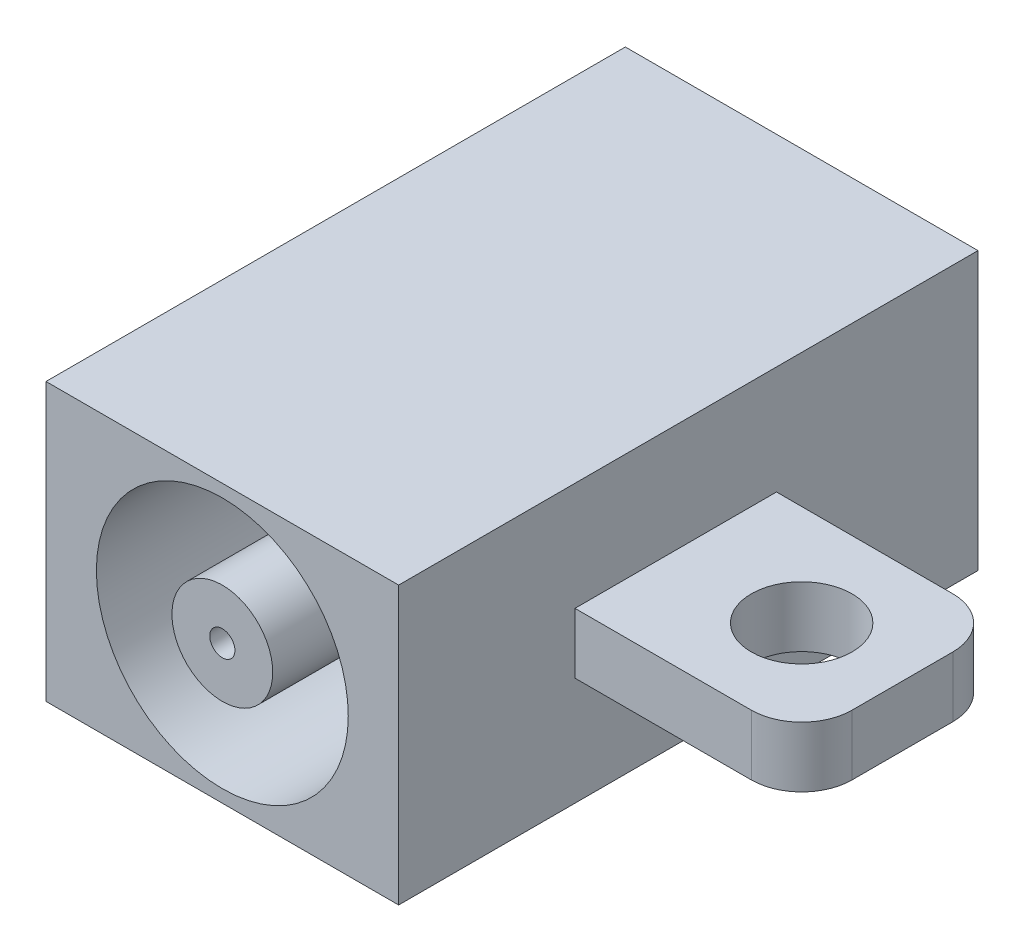
SolidWorks part; units mm, degrees
ref_plane "Front Plane" through (0, 0, 0) normal (0, 0, 1) x (1, 0, 0)
ref_plane "Top Plane" through (0, 0, 0) normal (0, 1, 0) x (1, 0, 0)
ref_plane "Right Plane" through (0, 0, 0) normal (1, 0, 0) x (0, 0, -1)
sketch "Sketch1" plane through (0, 0, 0) normal (0, 1, 0) x (1, 0, 0)
  line L1 (0, 0) -> (7, 0)
  line L2 (0, 0) -> (0, 11.5)
  line L3 (0, 11.5) -> (7, 11.5)
  line L4 (7, 0) -> (7, 11.5)
  dimension "D1" = 11.5
  dimension "D2" = 7
extrude "Boss-Extrude1" add sketch "Sketch1" along normal blind 5.5
sketch "Sketch2" plane through (0, 0, 0) normal (0, 0, 1) x (1, 0, 0)
  line L1 (0, 0) -> (7, 0) construction
  line L2 (7, 5.5) -> (7, 0) construction
  circle A0 centre (3.5, 2.75) radius 2.5
  dimension "D1" = 5
  dimension "D2" = 2.75
  dimension "D3" = 3.5
extrude "Cut-Extrude1" cut sketch "Sketch2" against normal blind 5.5
sketch "Sketch3" plane through (0, 0, 0) normal (0, 0, 1) x (1, 0, 0)
  circle A0 centre (3.5, 2.75) radius 1
  dimension "D1" = 2
extrude "Boss-Extrude2" add sketch "Sketch3" against normal blind 5.5
sketch "Sketch4" plane through (0, 0, 0) normal (0, 0, 1) x (1, 0, 0)
  circle A0 centre (3.5, 2.75) radius 0.25
  dimension "D1" = 0.5
extrude "Cut-Extrude2" cut sketch "Sketch4" against normal blind 5.5
sketch "Sketch5" plane through (7, 0, 0) normal (1, 0, 0) x (0, 0, -1)
  line L0 (0, 5.5) -> (0, 0) construction
  line L1 (3.5, 3.35) -> (7.5, 3.35)
  line L2 (3.5, 3.35) -> (3.5, 2.15)
  line L3 (3.5, 2.15) -> (7.5, 2.15)
  line L4 (7.5, 3.35) -> (7.5, 2.15)
  line L6 (0, 0) -> (11.5, 0) construction
  dimension "D1" = 3.5
  dimension "D2" = 1.2
  dimension "D3" = 4
  dimension "D4" = 2.15
extrude "Boss-Extrude3" add sketch "Sketch5" along normal blind 4.5
fillet "Fillet1" radius 1 2 edges at (11.5, 2.75, -7.5) (11.5, 2.75, -3.5)
sketch "Sketch6" plane through (0, 3.35, 0) normal (0, 1, 0) x (1, 0, 0)
  line L1 (10.5, 3.5) -> (7, 3.5) construction
  line L2 (11.5, 6.5) -> (11.5, 4.5) construction
  circle A0 centre (9.5, 5.5) radius 1
  dimension "D1" = 2
  dimension "D2" = 2
  dimension "D3" = 2
extrude "Cut-Extrude3" cut sketch "Sketch6" against normal up to next
